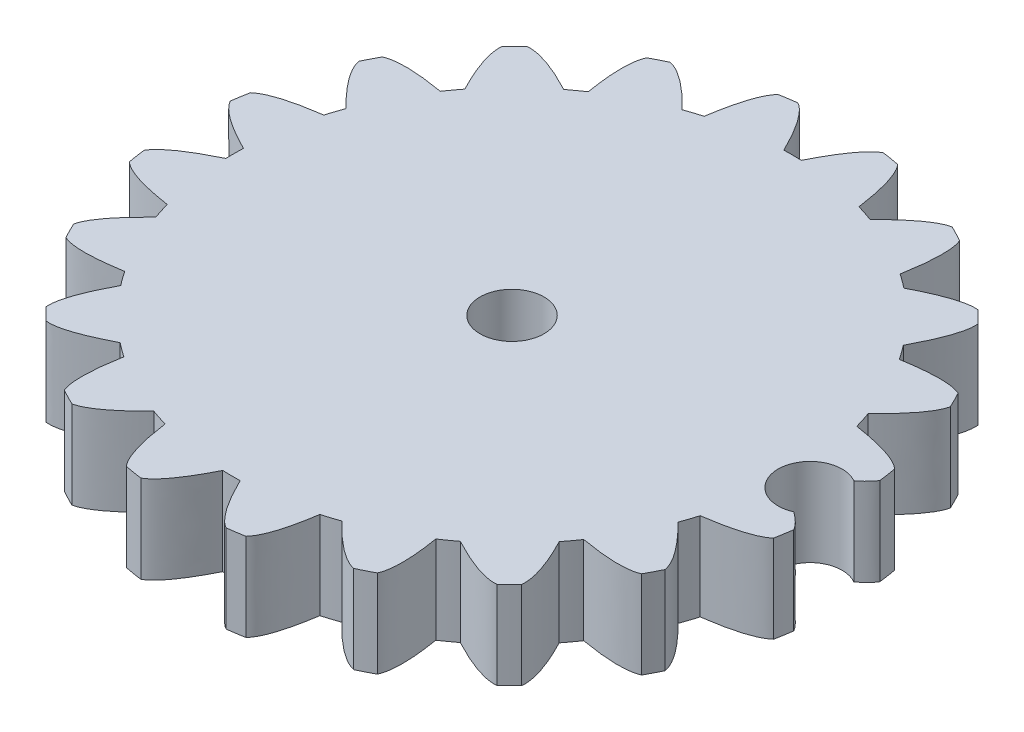
SolidWorks part; units mm, degrees
material "ABS"
ref_plane "Front Plane" through (0, 0, 0) normal (0, 0, 1) x (1, 0, 0)
ref_plane "Top Plane" through (0, 0, 0) normal (0, 1, 0) x (1, 0, 0)
ref_plane "Right Plane" through (0, 0, 0) normal (1, 0, 0) x (0, 0, -1)
sketch "Sketch1" plane through (0, 0, 0) normal (0, 1, 0) x (1, 0, 0)
  line L0 (9.8268, 12.5194) -> (12.6316, 9.6823) construction
  line L2 (11.2292, 11.1009) -> (13.3627, 13.21) construction
  line L3 (13.3627, 13.21) -> (13.5006, 13.3464)
  circle A0 centre (0, 0) radius 15.9155
  circle A1 centre (0, 0) radius 18.79
  spline S0 degree 2 poles (12.6316, 9.6823) (15.7721, 15.5919) (9.8268, 12.5194) knots 0 0 0 1 1 1
  point P3 (9.8268, 12.5194)
  point P4 (12.6316, 9.6823)
  point P6 (13.0064, 13.5609)
  point P12 (9.0213, 13.1118)
  point P14 (13.5006, 13.3464)
  point P15 (13.7094, 12.8497)
  point P16 (6.7275, 14.4237)
  dimension "D1" = 31.831
  dimension "D4" = 3
  dimension "D5" = 1
  dimension "D2" = 4
  dimension "D3" = 1
extrude "Boss-Extrude4" add sketch "Sketch1" along normal blind 5 contours A0 | A0 S0 A1 region at (12.1535, 0, -12.0146) region at (0, 0, 0)
pattern_circular "CirPattern6" count 20 every 18 about axis through (0, 5, 0) along (0, 1, 0) of "Boss-Extrude4"
sketch "Sketch2" plane through (0, 5, 0) normal (0, 1, 0) x (1, 0, 0)
  circle A0 centre (0, 0) radius 1.825
  circle A1 centre (17, 0) radius 1.825
  dimension "D1" = 3.65
  dimension "D2" = 3.65
  dimension "D3" = 17
extrude "Cut-Extrude1" cut sketch "Sketch2" against normal up to surface (5 mm away) up to face at (0, 0, 0)
equation "\"number-of-teeth\"= 20"
equation "\"gear-size\"= 4mm"
equation "\"circumference\"= \"number-of-teeth\" * ( ( 1 + \"space-between-teeth\" ) * \"gear-size\" )"
equation "\"space-between-teeth\"= .25"
equation "\"D1@Sketch1\" = \"circumference\" / pi"
equation "\"D2@Sketch1\"=\"gear-size\""
equation "\"gear-length\"= 3mm"
equation "\"D4@Sketch1\"=\"gear-length\""
equation "\"D5@Sketch1\"=\"gear-size\" * \"space-between-teeth\""
equation "\"D3@Sketch1\"=\"gear-size\" * \"space-between-teeth\""
equation "\"D1@CirPattern6\"=\"number-of-teeth\""
equation "\"D2@CirPattern6\"=360 / \"number-of-teeth\""
